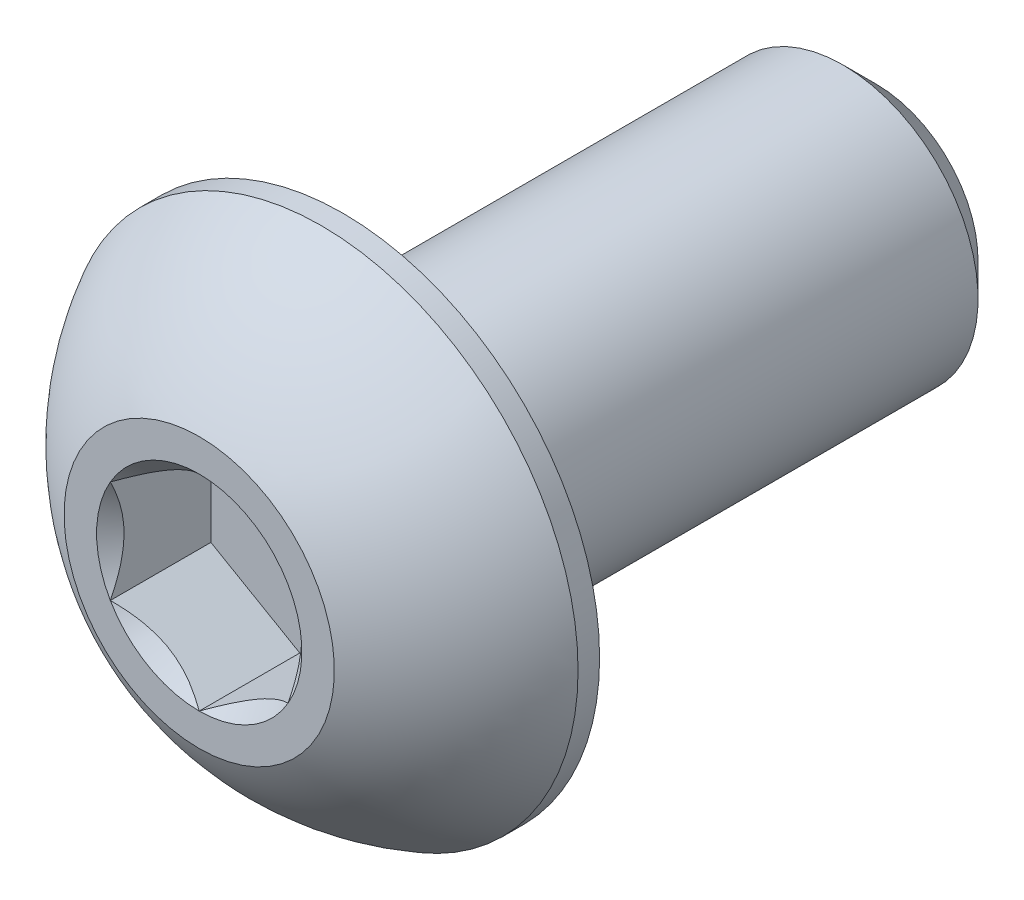
SolidWorks part; units mm, degrees
material "AISI 304"
ref_plane "Front" through (0, 0, 0) normal (0, 0, 1) x (1, 0, 0)
ref_plane "Top" through (0, 0, 0) normal (0, 1, 0) x (1, 0, 0)
ref_plane "Right" through (0, 0, 0) normal (1, 0, 0) x (0, 0, -1)
sketch "Sketch1" plane through (0, 0, 0) normal (1, 0, 0) x (0, 0, -1)
  line L2 (2.5654, 2.413) -> (12.0904, 2.413)
  line L3 (12.0904, 2.413) -> (12.0904, 0)
  line L4 (12.0904, 0) -> (2.5654, 0)
  line L6 (2.1806, 4.5847) -> (2.5654, 4.5847) construction
  line L7 (12.0904, 2.413) -> (12.0904, -2.413) construction
  line L8 (0, 0) -> (2.5654, 0) construction
  line L9 (2.5654, 4.5847) -> (2.5654, -4.5847) construction
  line L11 (2.5654, 2.413) -> (2.5654, 0)
  line L13 (0, 1.5875) -> (0, -1.5875) construction
  line L14 (0, 1.5875) -> (0, 2.413) construction
  arc A3 (0, 2.413) -> (2.1806, 4.5847) centre (4.5749, 0) cw construction
  dimension "D1" = 0.3848
revolve "Revolve1" add sketch "Sketch1" angle 360 mid plane about L4
sketch "Sketch3" plane through (0, 0, -12.0904) normal (0, 0, -1) x (-1, 0, 0)
  circle A0 centre (0, 0) radius 2.413
curve "Helix/Spiral1" pitch 0.7937 height 10.3188 turns 13
sketch "Sketch2" plane through (0, 0, 0) normal (1, 0, 0) x (0, 0, -1)
  line L0 (12.0904, 2.413) -> (12.7849, 2.413)
  line L1 (12.7849, 2.413) -> (12.4873, 1.8974)
  line L2 (12.4873, 1.8974) -> (12.3881, 1.8974)
  line L3 (12.3881, 1.8974) -> (12.0904, 2.413)
  line L4 (12.2392, 2.1552) -> (12.6361, 2.1552) construction
  dimension "D1" = 60
  dimension "D2" = 0.0992
  dimension "D3" = 0.3969
chamfer "Chamfer1" distance 0.5953 angle 45 1 edges at (0, 2.413, -12.0904)
sweep "Cut-Sweep1" [suppressed] cut profiles "Sketch2" path "Helix/Spiral1"
sketch "Sketch7" plane through (0, 0, 0) normal (1, 0, 0) x (0, 0, -1)
  line L6 (2.1806, 4.5847) -> (2.5654, 4.5847) construction
  line L8 (0, 0) -> (2.5654, 0) construction
  line L11 (2.5654, 4.5847) -> (2.5654, -4.5847) construction
  line L12 (2.1806, 4.5847) -> (2.5654, 4.5847)
  line L13 (0, 0) -> (2.5654, 0)
  line L14 (0, 1.5875) -> (0, -1.5875) construction
  line L15 (2.5654, 4.5847) -> (2.5654, 0)
  line L16 (0, 2.413) -> (0, 0)
  arc A2 (2.1806, 4.5847) -> (0, 2.413) centre (4.5749, 0) ccw construction
  arc A3 (2.1806, 4.5847) -> (0, 2.413) centre (4.5749, 0) ccw
revolve "Revolve2" add sketch "Sketch7" angle 360 mid plane about L13
sketch "Sketch5" plane through (0, 0, 0) normal (0, 0, 1) x (1, 0, 0)
  line L1 (1.5875, -0.9165) -> (1.5875, 0.9165)
  line L2 (1.5875, 0.9165) -> (0, 1.8331)
  line L3 (0, 1.8331) -> (-1.5875, 0.9165)
  line L4 (-1.5875, 0.9165) -> (-1.5875, -0.9165)
  line L5 (-1.5875, -0.9165) -> (0, -1.8331)
  line L6 (0, -1.8331) -> (1.5875, -0.9165)
  circle A0 centre (0, 0) radius 1.5875 construction
extrude "Cut-Extrude2" cut sketch "Sketch5" against normal blind 1.7958
sketch "Sketch6" plane through (0, 0, 0) normal (0, 0, 1) x (1, 0, 0)
  circle A0 centre (0, 0) radius 1.8331
extrude "Cut-Extrude3" cut sketch "Sketch6" against normal blind 1.7958 draft 45
sketch "Sketch9" [suppressed] plane through (0, 0, -2.5654) normal (0, 0, 1) x (1, 0, 0)
  circle A2 centre (0, 0) radius 2.413
extrude "Boss-Extrude2" [suppressed] add sketch "Sketch9" against normal offset from surface (9.525 mm away) 31.75
sketch "Sketch10" plane through (0, 0, 0) normal (1, 0, 0) x (0, 0, -1)
  line L0 (12.0904, 2.413) -> (12.0904, -2.413) construction
  point P0 (10.8998, -2.413)
  dimension "D1" = 1.1906
equation "\"D3@Helix/Spiral1\" = \"Lg@Sketch1\" + \"D4@Helix/Spiral1\""
equation "\"D2@Sketch2\" = \"D4@Helix/Spiral1\" * .125"
equation "\"D3@Sketch2\" = \"D4@Helix/Spiral1\" * .5"
equation "\"D1@Chamfer1\" = \"D4@Helix/Spiral1\" * .75"
equation "\"D1@Cut-Extrude2\" = \"Head Ht@Sketch1\" * .7"
equation "\"D1@Sketch1\" = \"Head Ht@Sketch1\" * .15"
equation "\"D1@Sketch10\" = \"D4@Helix/Spiral1\" * 1.5"
equation "\"D1@Cut-Extrude3\" = \"D1@Cut-Extrude2\""
